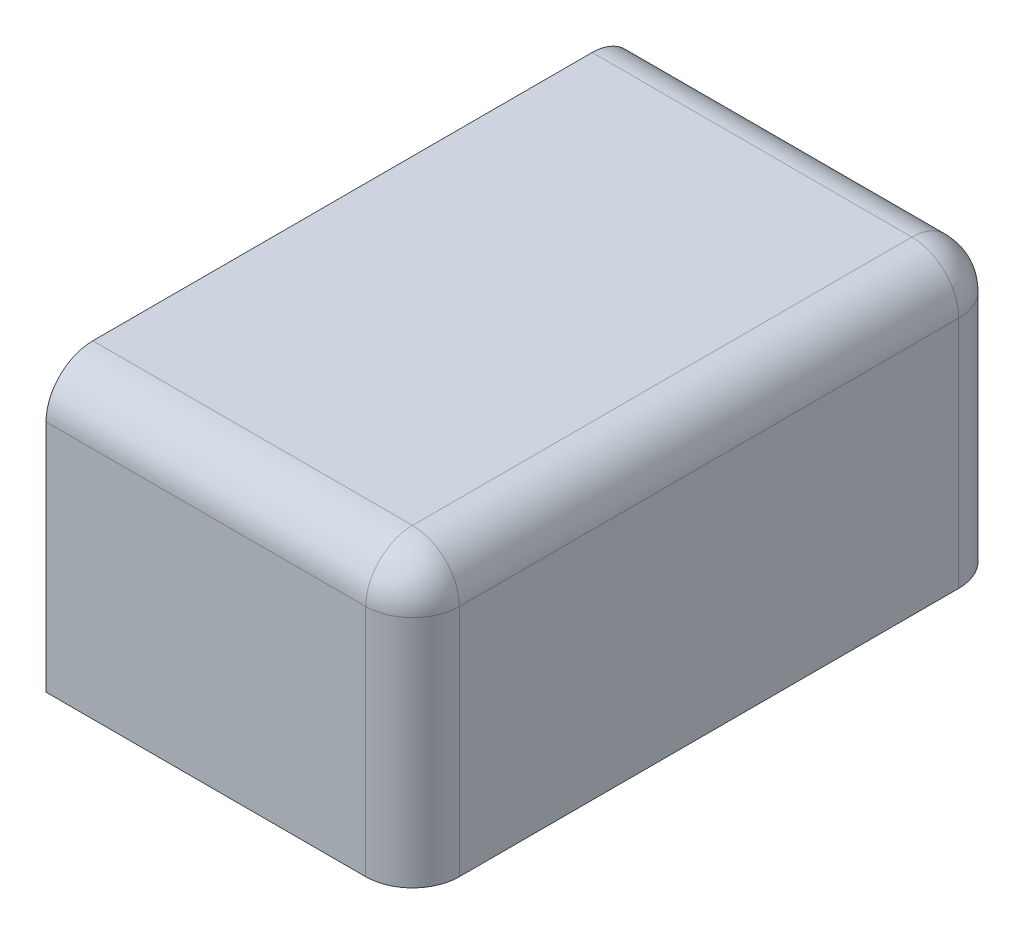
SolidWorks part; units mm, degrees
ref_plane "Front Plane" through (0, 0, 0) normal (0, 0, 1) x (1, 0, 0)
ref_plane "Top Plane" through (0, 0, 0) normal (0, 1, 0) x (1, 0, 0)
ref_plane "Right Plane" through (0, 0, 0) normal (1, 0, 0) x (0, 0, -1)
ref_axis "Axis X" through (-88.99, 0, 0) along (1, 0, 0)
ref_axis "Axis Y" through (0, 55, 0) along (0, -1, 0)
ref_axis "Axis Z" through (0, 0, -88.99) along (0, 0, 1)
sketch "Sketch1" plane through (0, 0, 0) normal (0, 1, 0) x (1, 0, 0)
  line L1 (-18.6436, -30.1625) -> (18.6436, -30.1625)
  line L2 (-18.6436, -30.1625) -> (-18.6436, 30.1625)
  line L3 (-18.6436, 30.1625) -> (18.6436, 30.1625)
  line L4 (18.6436, -30.1625) -> (18.6436, 30.1625)
  line L5 (-18.6436, -30.1625) -> (18.6436, 30.1625) construction
  line L6 (-18.6436, 30.1625) -> (18.6436, -30.1625) construction
  point P0 (0, 0)
  dimension "D1" = 60.325
  dimension "D2" = 37.2872
extrude "Boss-Extrude1" add sketch "Sketch1" along normal blind 28.575
fillet "Fillet1" radius 4.7625 5 edges at (0, 28.575, -30.1625) (18.6436, 28.575, 0) (0, 28.575, 30.1625) (18.6436, 14.2875, -30.1625) (18.6436, 14.2875, 30.1625)
shell "Shell1" thickness 1.5875 removed face at (-18.6436, 17.7913, 0) removed face at (4.9558, 0, 0)
